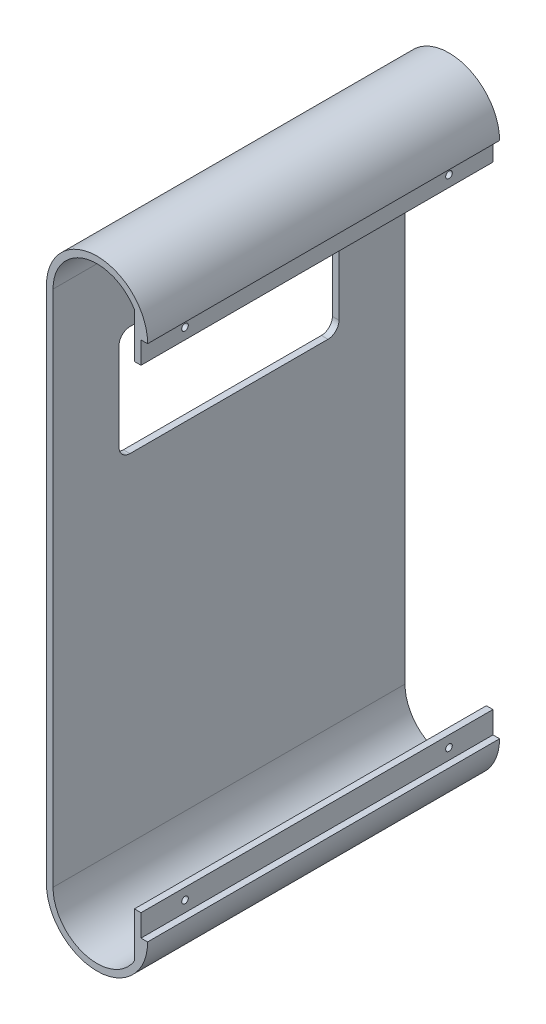
SolidWorks part; units mm, degrees
ref_plane "Front Plane" through (0, 0, 0) normal (0, 0, 1) x (1, 0, 0)
ref_plane "Top Plane" through (0, 0, 0) normal (0, 1, 0) x (1, 0, 0)
ref_plane "Right Plane" through (0, 0, 0) normal (1, 0, 0) x (0, 0, -1)
sketch "Sketch1" plane through (0, 0, 0) normal (0, 0, 1) x (1, 0, 0)
  line L0 (0, -75) -> (-40, -75) construction
  line L1 (33, 42.75) -> (-40, 42.75) construction
  line L3 (-40, -75) -> (-40, 160.5)
  line L4 (-43, -75) -> (-43, 160.5)
  line L5 (0, 160.5) -> (3, 160.5)
  line L6 (0, -75) -> (3, -75)
  arc A0 (-40, -75) -> (0, -75) centre (-20, -75) ccw
  arc A1 (-40, 160.5) -> (0, 160.5) centre (-20, 160.5) cw
  arc A2 (-43, 160.5) -> (3, 160.5) centre (-20, 160.5) cw
  arc A3 (-43, -75) -> (3, -75) centre (-20, -75) ccw
  dimension "D1" = 3
extrude "Boss-Extrude1" add sketch "Sketch1" against normal up to surface (160 mm away)
ref_plane "Plane1" through (3, 0, 0) normal (1, 0, 0) x (0, 0, -1)
sketch "Sketch5" plane through (0, 0, -160) normal (0, 0, -1) x (-1, 0, 0)
  line L0 (43, 42.75) -> (-4.5, 42.75) construction
  line L1 (3, -65) -> (0, -65)
  line L2 (3, -65) -> (3, -86.3578)
  line L3 (3, -86.3578) -> (0, -86.3578)
  line L4 (0, -65) -> (0, -86.3578)
  line L5 (43, 160.5) -> (43, -75) construction
  line L6 (0, 150.5) -> (0, 171.8578)
  line L7 (3, 171.8578) -> (0, 171.8578)
  line L8 (3, 150.5) -> (3, 171.8578)
  line L9 (3, 150.5) -> (0, 150.5)
  arc A0 (-3, -75) -> (43, -75) centre (20, -75) ccw construction
extrude "Boss-Extrude4" add sketch "Sketch5" against normal up to surface (160 mm away) up to face at (-20, 42.75, 0)
sketch "Sketch7" plane through (-3, 0, 0) normal (-1, 0, 0) x (0, 0, 1)
  line L0 (0, -65) -> (-160, -65) construction
  line L1 (0, -65) -> (-160, -65) construction
  line L2 (0, 150.5) -> (-160, 150.5) construction
  line L3 (0, 150.5) -> (-160, 150.5) construction
  line L4 (-160, 160.5) -> (-160, -75) construction
  line L5 (0, 160.5) -> (0, -75) construction
  line L6 (-160, 42.75) -> (0, 42.75) construction
  circle A0 centre (-140, -70) radius 1.5
  circle A1 centre (-20, -70) radius 1.5
  circle A2 centre (-20, 155.5) radius 1.5
  circle A3 centre (-140, 155.5) radius 1.5
  dimension "D1" = 5
  dimension "D2" = 20
  dimension "D4" = 5
  dimension "D3" = 20
extrude "Cut-Extrude2" cut sketch "Sketch7" against normal through all
sketch "Sketch8" plane through (-43, 0, 0) normal (-1, 0, 0) x (0, 0, 1)
  line L0 (-30, 123.2573) -> (-30, 83.2573) construction
  line L1 (-125, 128.2573) -> (-35, 128.2573)
  line L2 (-130, 123.2573) -> (-130, 83.2573)
  line L3 (-125, 78.2573) -> (-35, 78.2573)
  line L4 (-30, 123.2573) -> (-30, 83.2573)
  line L5 (-35, 78.2573) -> (-125, 78.2573) construction
  line L6 (-130, 83.2573) -> (-130, 123.2573) construction
  line L7 (-125, 128.2573) -> (-35, 128.2573) construction
  arc A0 (-125, 128.2573) -> (-130, 123.2573) centre (-125, 123.2573) ccw
  arc A1 (-130, 83.2573) -> (-125, 78.2573) centre (-125, 83.2573) ccw
  arc A2 (-35, 78.2573) -> (-30, 83.2573) centre (-35, 83.2573) ccw
  arc A3 (-35, 128.2573) -> (-30, 123.2573) centre (-35, 123.2573) cw
  dimension "D5" = 5
  dimension "D1" = 0
  dimension "D2" = 0
  dimension "D3" = 0
  dimension "D4" = 0
extrude "Cut-Extrude3" cut sketch "Sketch8" against normal up to surface (3 mm away) up to face at (-40, 42.75, -80)
